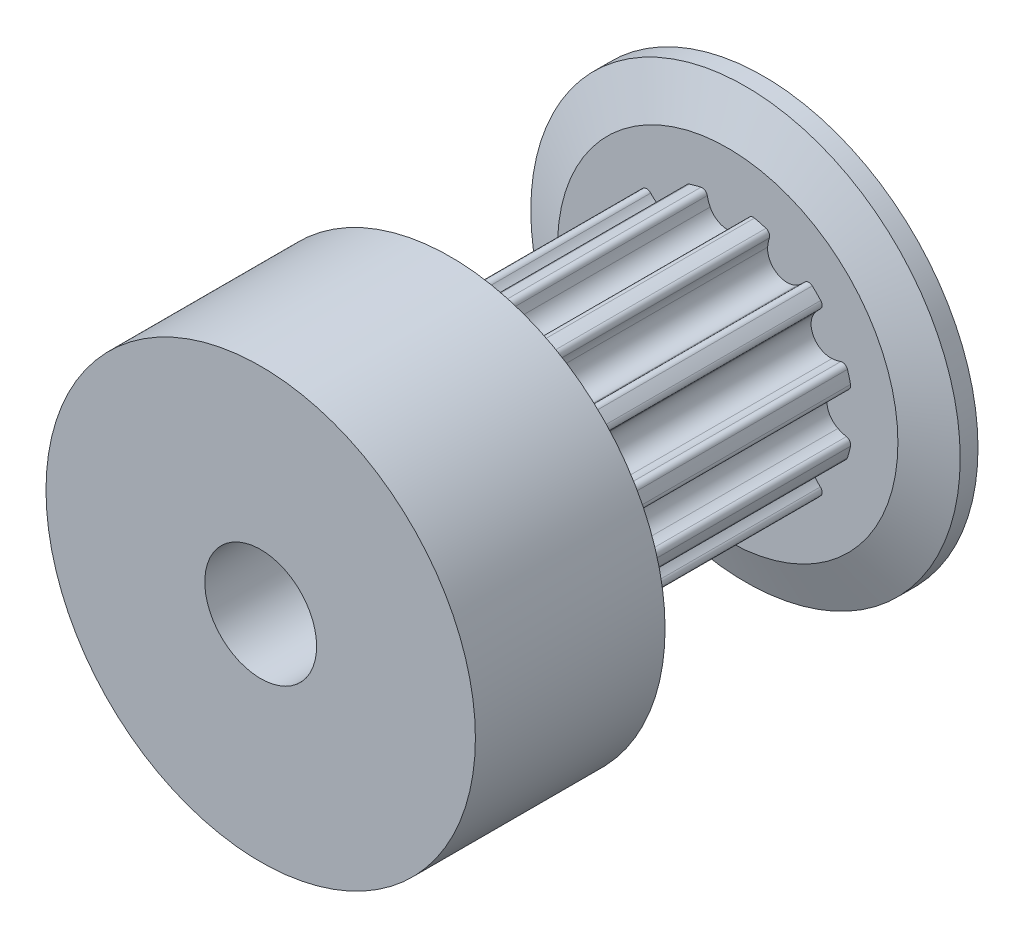
SolidWorks part; units mm, degrees
ref_plane "Front Plane" through (0, 0, 0) normal (0, 0, 1) x (1, 0, 0)
ref_plane "Top Plane" through (0, 0, 0) normal (0, 1, 0) x (1, 0, 0)
ref_plane "Right Plane" through (0, 0, 0) normal (1, 0, 0) x (0, 0, -1)
sketch "Sketch1" plane through (0, 0, 0) normal (0, 0, 1) x (1, 0, 0)
  line L1 (-1.6491, 2.8185) -> (1.6491, 2.8185) construction
  line L4 (0, 0) -> (0, 2.8185) construction
  line L5 (0, 2.8185) -> (0, 9.5178) construction
  line L6 (0, 3.8225) -> (1.9303, 3.2993) construction
  line L7 (1.9303, 3.2993) -> (2.4111, 3.018) construction
  line L8 (1.9303, 3.2993) -> (1.6491, 2.8185) construction
  line L9 (-1.9303, 3.2993) -> (-1.6491, 2.8185) construction
  line L10 (-1.8021, 3.08) -> (-3.5667, 6.096)
  line L11 (-3.5667, 6.096) -> (3.5667, 6.096)
  line L12 (3.5667, 6.096) -> (1.8021, 3.08)
  circle A0 centre (0, 0) radius 3.8225 construction
  circle A1 centre (0, 0) radius 6.096 construction
  circle A2 centre (0, 0) radius 3.5685 construction
  arc A3 (-0.4989, 3.1303) -> (0.4989, 3.1303) centre (0, 3.3735) ccw
  arc A4 (-0.4989, 3.1303) -> (-0.5801, 3.37) centre (0.4, 3.5685) cw
  arc A5 (-1.8021, 3.08) -> (-0.759, 3.4868) centre (0, 0) cw
  arc A6 (-0.5801, 3.37) -> (-0.759, 3.4868) centre (-0.7271, 3.3403) ccw
  arc A7 (1.8021, 3.08) -> (0.759, 3.4868) centre (0, 0) ccw
  arc A8 (0.5801, 3.37) -> (0.759, 3.4868) centre (0.7271, 3.3403) cw
  arc A9 (0.4989, 3.1303) -> (0.5801, 3.37) centre (-0.4, 3.5685) ccw
  point P4 (0, 0)
  point P6 (0, 20.9083)
  point P11 (0, 3.8225)
  point P13 (0, 6.096)
  point P14 (0, 3.5685)
  dimension "D1" = 11.3906
  dimension "D2" = 5.6953
sketch "Sketch2" plane through (0, 0, 0) normal (1, 0, 0) x (0, 0, -1)
  line L0 (-7.135, 1.5875) -> (7.135, 1.5875)
  line L1 (-7.135, 1.5875) -> (-7.135, 6.096)
  line L2 (-1.75, 6.096) -> (-7.135, 6.096)
  line L3 (-2.255, 1.5875) -> (-2.255, 6.096) construction
  line L4 (-2.255, 6.096) -> (-1.245, 6.096) construction
  line L5 (-1.245, 6.096) -> (-1.245, 3.5685) construction
  line L6 (-1.245, 3.5685) -> (6.125, 3.5685)
  line L7 (6.125, 3.5685) -> (6.125, 6.096) construction
  line L8 (6.125, 6.096) -> (7.135, 6.096) construction
  line L9 (7.135, 6.096) -> (7.135, 1.5875)
  line L10 (-7.135, 0) -> (7.135, 0) construction
  line L11 (6.63, 6.096) -> (6.125, 4.8323)
  line L12 (-1.245, 4.8323) -> (-1.75, 6.096)
  line L14 (-1.245, 4.8323) -> (-1.245, 3.5685)
  line L15 (6.125, 3.5685) -> (6.125, 4.8323)
  line L16 (6.63, 6.096) -> (7.135, 6.096)
  arc A0 (-1.245, 4.8323) -> (-1.75, 6.096) centre (-3.0788, 4.8323) ccw construction
  arc A1 (6.125, 4.8323) -> (6.63, 6.096) centre (7.9588, 4.8323) cw construction
  point P12 (-1.245, 4.8323)
  point P14 (-1.75, 6.096)
  point P20 (6.125, 4.8323)
  point P21 (6.63, 6.096)
  point P25 (6.125, 0)
  point P26 (-1.245, 0)
  dimension "OA" = 14.27
  dimension "Bore" = 3.175
  dimension "Inside Width" = 7.37
revolve "Revolve1" add sketch "Sketch2" angle 360 mid plane about L10
sketch "Sketch3" plane through (0, 0, 0) normal (0, 0, 1) x (1, 0, 0)
  line L6 (3.5667, 6.096) -> (-3.5667, 6.096)
  line L7 (1.8021, 3.08) -> (3.5667, 6.096)
  line L8 (-3.5667, 6.096) -> (-1.8021, 3.08)
  line L9 (3.5667, 6.096) -> (-3.5667, 6.096)
  line L10 (1.8021, 3.08) -> (3.5667, 6.096)
  line L11 (-3.5667, 6.096) -> (-1.8021, 3.08)
  arc A8 (1.8021, 3.08) -> (0.759, 3.4868) centre (0, 0) ccw
  arc A9 (0.759, 3.4868) -> (0.5801, 3.37) centre (0.7271, 3.3403) ccw
  arc A10 (0.4989, 3.1303) -> (0.5801, 3.37) centre (-0.4, 3.5685) ccw
  arc A11 (-0.4989, 3.1303) -> (0.4989, 3.1303) centre (0, 3.3735) ccw
  arc A12 (-0.5801, 3.37) -> (-0.4989, 3.1303) centre (0.4, 3.5685) ccw
  arc A13 (-0.5801, 3.37) -> (-0.759, 3.4868) centre (-0.7271, 3.3403) ccw
  arc A14 (-0.759, 3.4868) -> (-1.8021, 3.08) centre (0, 0) ccw
  arc A15 (1.8021, 3.08) -> (0.759, 3.4868) centre (0, 0) ccw
  arc A16 (0.759, 3.4868) -> (0.5801, 3.37) centre (0.7271, 3.3403) ccw
  arc A17 (0.4989, 3.1303) -> (0.5801, 3.37) centre (-0.4, 3.5685) ccw
  arc A18 (-0.4989, 3.1303) -> (0.4989, 3.1303) centre (0, 3.3735) ccw
  arc A19 (-0.5801, 3.37) -> (-0.4989, 3.1303) centre (0.4, 3.5685) ccw
  arc A20 (-0.5801, 3.37) -> (-0.759, 3.4868) centre (-0.7271, 3.3403) ccw
  arc A21 (-0.759, 3.4868) -> (-1.8021, 3.08) centre (0, 0) ccw
  dimension "D1" = 0
extrude "Cut-Extrude1" cut sketch "Sketch3" against normal up to vertex (6.125 mm away) from vertex up to point (0, 3.5685, -6.125) starting at point (0, 3.5685, 1.245)
pattern_circular "CirPattern1" count 12 over 360 about axis through (0, 0, 7.135) along (0, 0, 1) of "Cut-Extrude1"
sketch "Sketch4" plane through (0, 0, 0) normal (1, 0, 0) x (0, -1, 0)
  line L0 (0, -1.245) -> (0, -7.135) construction
  line L1 (-1.5875, -7.135) -> (1.5875, -7.135) construction
  line L2 (4.8323, -1.245) -> (-4.8323, -1.245) construction
  circle A0 centre (0, -4.19) radius 1.4224
extrude "Cut-Extrude2" [suppressed] cut sketch "Sketch4" along normal through all
ref_plane "Plane1" [suppressed] through (0, 0, 4.19) normal (0, 0, 1) x (1, 0, 0)
sketch "Sketch5" [suppressed] plane through (0, 0, 4.19) normal (0, 0, 1) x (1, 0, 0)
  line L0 (0, 0) -> (0, 6.096) construction
  line L1 (1.5875, -1.0414) -> (1.5875, 0)
  line L2 (1.9685, -1.4224) -> (5.5467, -1.4224)
  line L3 (1.5875, 0) -> (6.096, 0) construction
  line L4 (1.5875, 0) -> (5.9277, 0)
  line L5 (5.9277, 0) -> (5.9277, -1.0414)
  line L6 (1.9685, -1.4224) -> (1.5875, -1.0414)
  line L7 (5.9277, -1.0414) -> (5.5467, -1.4224)
  circle A0 centre (0, 0) radius 6.096 construction
  circle A1 centre (0, 0) radius 1.5875 construction
  point P2 (1.5875, -1.4224)
  point P11 (5.9277, -1.4224)
revolve "Revolve2" [suppressed] add sketch "Sketch5" angle 360 mid plane about L4
sketch "Sketch6" [suppressed] plane through (5.9277, 5.3841, 0) normal (-1, 0, 0) x (0, -1, 0)
  line L1 (5.3841, 5.0112) -> (4.6729, 4.6006)
  line L2 (4.6729, 4.6006) -> (4.6729, 3.7794)
  line L3 (4.6729, 3.7794) -> (5.3841, 3.3688)
  line L4 (5.3841, 3.3688) -> (6.0953, 3.7794)
  line L5 (6.0953, 3.7794) -> (6.0953, 4.6006)
  line L6 (6.0953, 4.6006) -> (5.3841, 5.0112)
  circle A0 centre (5.3841, 4.19) radius 0.7112 construction
  dimension "D1" = 1.4224
extrude "Cut-Extrude3" [suppressed] cut sketch "Sketch6" along normal blind 1.0668
chamfer "Chamfer1" [suppressed] distance 0.2807 angle 45
ref_axis "Center Axis 1" through (0, 0, -7.135) along (0, 0, 1)
ref_plane "Contact Plane 1" through (0, 0, 7.135) normal (0, 0, 1) x (1, 0, 0)
ref_plane "Contact Plane 2" through (0, 0, -7.135) normal (0, 0, -1) x (-1, 0, 0)
equation "\"D2@Sketch1\"= \"D1@Sketch1\" / 2"
equation "\"D1@Sketch6\" = \"Set Screw@Sketch4\" / 2"
equation "\"D1@Cut-Extrude3\" = \"D1@Sketch6\"*.75"
